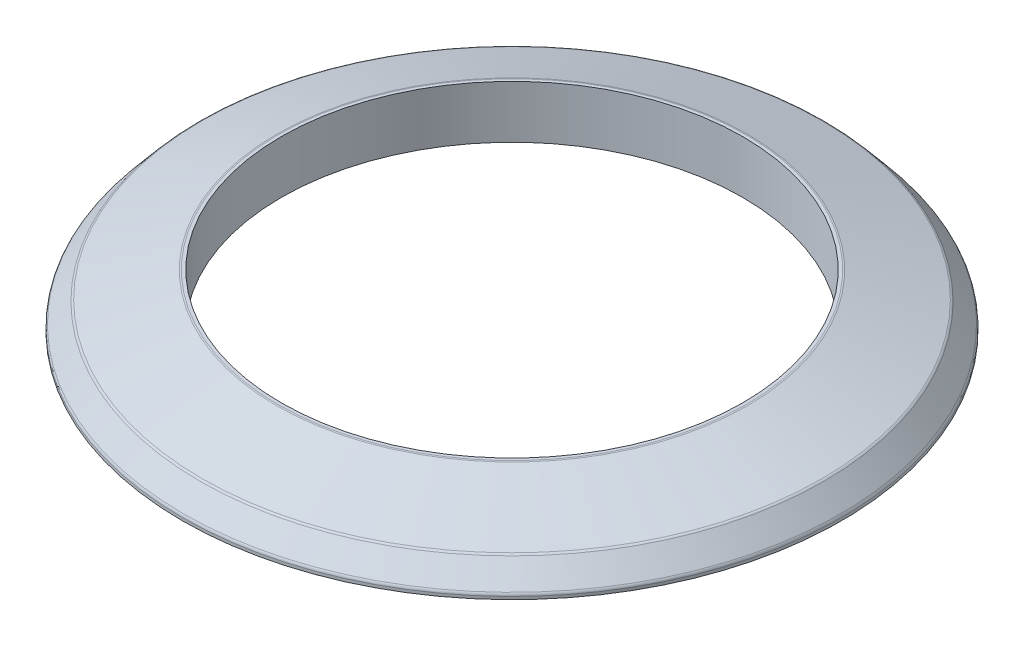
SolidWorks part; units mm, degrees
ref_plane "Front Plane" through (0, 0, 0) normal (0, 0, 1) x (1, 0, 0)
ref_plane "Top Plane" through (0, 0, 0) normal (0, 1, 0) x (1, 0, 0)
ref_plane "Right Plane" through (0, 0, 0) normal (1, 0, 0) x (0, 0, -1)
sketch "Sketch1" plane through (0, 0, 0) normal (0, 1, 0) x (1, 0, 0)
  circle A0 centre (0, 0) radius 19.05
  circle A1 centre (0, 0) radius 13.335
  dimension "D1" = 38.1
  dimension "D2" = 26.67
extrude "Extrude1" add sketch "Sketch1" along normal blind 1.524
chamfer "Chamfer1" distance 1.27 angle 40 1 edges at (0, 1.524, 19.05) first distance on face at (0, 1.524, 19.05)
sketch "Sketch2" plane through (0, 1.524, 0) normal (0, 1, 0) x (-1, 0, 0)
  circle A0 centre (0, 0) radius 17.9843
  circle A1 centre (0, 0) radius 13.335
extrude "Extrude2" add sketch "Sketch2" along normal blind 1.524
chamfer "Chamfer2" distance 1.524 angle 71 1 edges at (0, 3.048, 17.9843) first distance on face at (0, 3.048, 17.9843)
fillet "Fillet1" radius 0.254 3 edges at (0, 3.048, 13.5583) (0, 0.254, 19.05) (0, 1.524, 17.9843)
